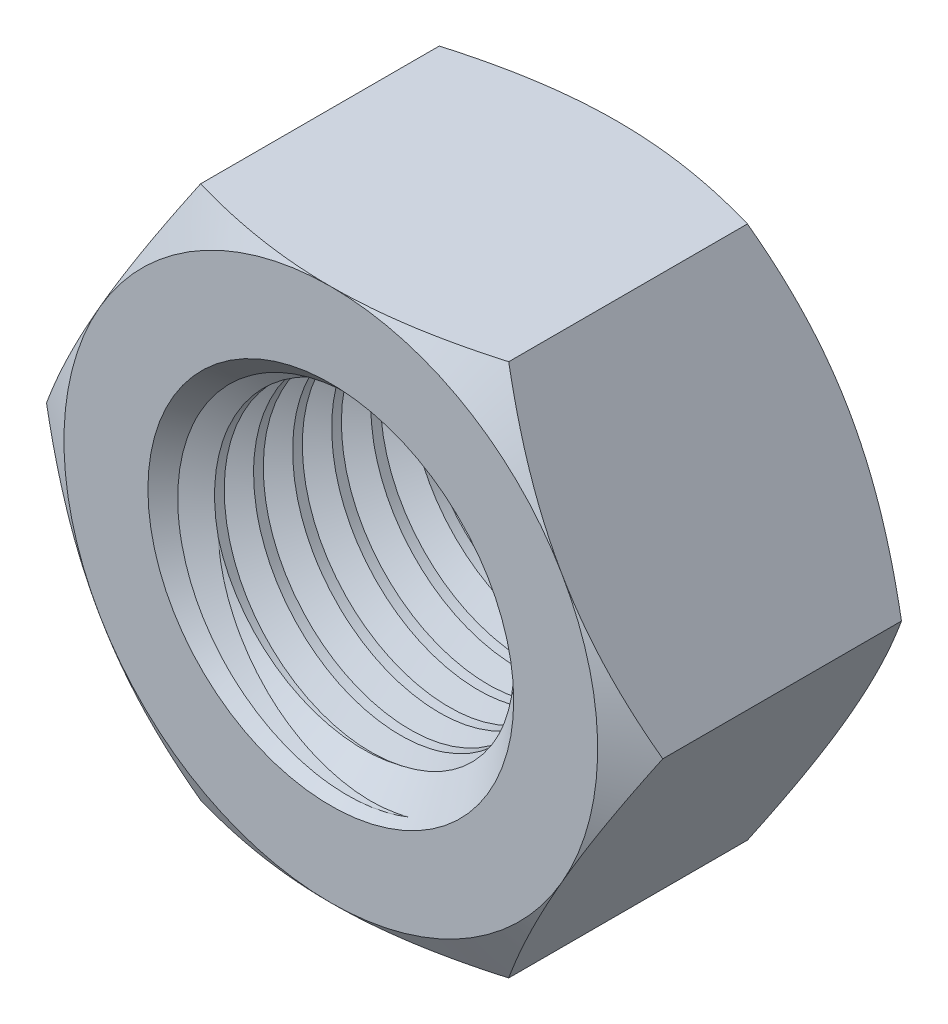
SolidWorks part; units mm, degrees
ref_plane "Front" through (0, 0, 0) normal (0, 0, 1) x (1, 0, 0)
ref_plane "Top" through (0, 0, 0) normal (0, 1, 0) x (1, 0, 0)
ref_plane "Right" through (0, 0, 0) normal (1, 0, 0) x (0, 0, -1)
sketch "Çizim1" plane through (0, 0, 0) normal (0, 0, 1) x (1, 0, 0)
  line L1 (23.6714, 0) -> (11.8357, 20.5)
  line L2 (11.8357, 20.5) -> (-11.8357, 20.5)
  line L3 (-11.8357, 20.5) -> (-23.6714, 0)
  line L4 (-23.6714, 0) -> (-11.8357, -20.5)
  line L5 (-11.8357, -20.5) -> (11.8357, -20.5)
  line L6 (11.8357, -20.5) -> (23.6714, 0)
  circle A0 centre (0, 0) radius 20.5 construction
  point P1 (0, 0)
  dimension "D1" = 41
extrude "Yükseklik-Ekstrüzyon1" add sketch "Çizim1" along normal blind 22
sketch "Çizim2" plane through (0, 0, 22) normal (0, 0, 1) x (1, 0, 0)
  circle A0 centre (0, 0) radius 20.5
extrude "Kes-Ekstrüzyon1" cut sketch "Çizim2" against normal blind 22 draft 60 flip side to cut
sketch "Çizim3" plane through (0, 0, 0) normal (0, 0, -1) x (-1, 0, 0)
  circle A0 centre (0, 0) radius 20.5
extrude "Kes-Ekstrüzyon2" cut sketch "Çizim3" against normal blind 22 draft 60 flip side to cut
sketch "Çizim4" plane through (0, 0, 0) normal (0, 0, -1) x (-1, 0, 0)
  circle A0 centre (0, 0) radius 11.55
  dimension "D1" = 23.1
extrude "Kes-Ekstrüzyon3" cut sketch "Çizim4" against normal blind 22
chamfer "Pah1" distance 2.5 angle 45 2 edges at (-11.55, 0, 22) (-11.55, 0, 0)
sketch "Çizim5" plane through (0, 0, 22) normal (0, 0, 1) x (1, 0, 0)
  circle A0 centre (0, 0) radius 11.55
curve "Helis/Spiral1" pitch 3 height 25 radius 11.55 centre (0, 0, 22) axis (0, 0, -1) start towards (1, 0, 0)
ref_plane "Düzlem1" through (-5.775, -10.0026, -3) normal (-0.8653, 0.4996, -0.0413) x (-0.0358, 0.0207, 0.9991)
sketch "Çizim6" plane through (-5.775, -10.0026, -3) normal (-0.8653, 0.4996, -0.0413) x (-0.0358, 0.0207, 0.9991)
  line L1 (0, -1.95) -> (1.4364, 0.5379)
  line L3 (-1.4364, 0.5379) -> (0, -1.95)
  line L4 (1.4364, 0.5379) -> (-1.4364, 0.5379)
  line L5 (1.6887, 0.975) -> (0, 0.975) [skipped]
  circle A0 centre (0, 0) radius 0.975 construction
  dimension "D1" = 1.95
sweep "Kes-Süpür1" cut profiles "Çizim6" path "Helis/Spiral1" align with end faces yes
